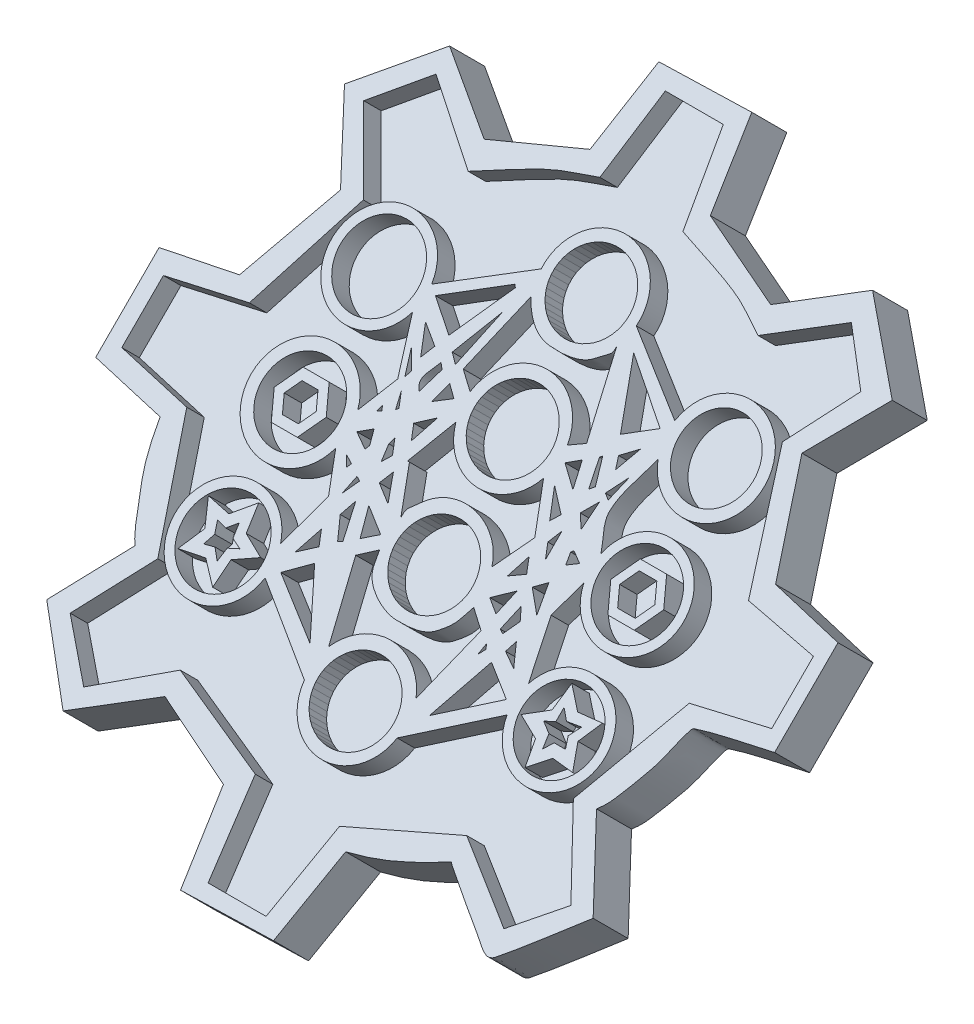
SolidWorks part; units mm, degrees
ref_plane "Front Plane" through (0, 0, 0) normal (0, 0, 1) x (1, 0, 0)
ref_plane "Top Plane" through (0, 0, 0) normal (0, 1, 0) x (1, 0, 0)
ref_plane "Right Plane" through (0, 0, 0) normal (1, 0, 0) x (0, 0, -1)
ref_plane "Plane2" through (0, -6.35, 0) normal (0, 1, 0) x (1, 0, 0)
sketch "Sketch2" plane through (0, -6.35, 0) normal (0, 1, 0) x (1, 0, 0)
  circle A0 centre (0, 0) radius 5.715
  dimension "D1" = 11.43
ref_axis "Axis1" through (-6.2865, 0, 0) along (1, 0, 0)
ref_plane "Plane1" through (0, 0, 0) normal (0, 0.7071, 0.7071) x (1, 0, 0)
sketch "Sketch3" plane through (0, 0, 0) normal (0, 0.7071, 0.7071) x (1, 0, 0)
  line L0 (0, 0) -> (-20.32, 0) construction
  line L1 (-6.2865, 0) -> (6.2865, 0) construction
  line L2 (-20.32, -38.1) -> (-20.32, 38.1) construction
  circle A0 centre (0, 0) radius 19.05
  point P3 (0, 0)
  point P13 (-20.32, 0)
  point P15 (-20.32, 7.62)
  point P16 (-20.32, -7.62)
  point P17 (-20.32, -22.86)
  dimension "D1" = 38.1
  dimension "D4" = 20.32
  dimension "D5" = 76.2
extrude "Boss-Extrude1" add sketch "Sketch3" along normal blind 6.35
extrude "Boss-Extrude2" add sketch "Sketch2" along normal up to surface and the other way blind 3.175 up to face at (0, -13.4704, 13.4704)
sketch "Sketch5" plane through (0, 4.4901, 4.4901) normal (0, 0.7071, 0.7071) x (1, 0, 0)
  line L0 (4.752, 20.3921) -> (4.7809, 21.0328)
  line L1 (4.7809, 21.0328) -> (4.7223, 21.6719)
  line L2 (4.7223, 21.6719) -> (4.5773, 22.2981)
  line L3 (4.5773, 22.2981) -> (4.3485, 22.9001)
  line L4 (4.3485, 22.9001) -> (4.0399, 23.4673)
  line L5 (4.0399, 23.4673) -> (3.6571, 23.9895)
  line L6 (3.6571, 23.9895) -> (3.2069, 24.4575)
  line L7 (3.2069, 24.4575) -> (2.6974, 24.8627)
  line L8 (2.6974, 24.8627) -> (2.1375, 25.1981)
  line L9 (2.1375, 25.1981) -> (1.5374, 25.4576)
  line L10 (1.5374, 25.4576) -> (0.9077, 25.6366)
  line L11 (0.9077, 25.6366) -> (0.2596, 25.732)
  line L12 (0.2596, 25.732) -> (-0.3952, 25.7419)
  line L13 (-0.3952, 25.7419) -> (-1.0451, 25.6662)
  line L14 (-1.0451, 25.6662) -> (-1.6785, 25.5063)
  line L15 (-1.6785, 25.5063) -> (-2.2841, 25.2651)
  line L16 (-2.2841, 25.2651) -> (-2.8511, 24.9468)
  line L17 (-2.8511, 24.9468) -> (-3.3694, 24.5571)
  line L18 (-3.3694, 24.5571) -> (-3.8296, 24.103)
  line L19 (-3.8296, 24.103) -> (-4.2237, 23.5925)
  line L20 (-4.2237, 23.5925) -> (-4.5445, 23.0349)
  line L21 (-4.5445, 23.0349) -> (-4.7864, 22.4399)
  line L22 (-4.7864, 22.4399) -> (-4.945, 21.8184)
  line L23 (-4.945, 21.8184) -> (-5.0175, 21.1812)
  line L24 (-5.0175, 21.1812) -> (-5.0026, 20.5399)
  line L25 (-5.0026, 20.5399) -> (-4.9006, 19.9058)
  line L26 (-4.9006, 19.9058) -> (-4.7133, 19.2903)
  line L27 (-4.7133, 19.2903) -> (-4.444, 18.7044)
  line L28 (-4.444, 18.7044) -> (-4.0976, 18.1585)
  line L29 (-4.0976, 18.1585) -> (-3.6801, 17.6623)
  line L30 (-3.6801, 17.6623) -> (-3.1992, 17.2247)
  line L31 (-3.1992, 17.2247) -> (-2.6633, 16.8536)
  line L32 (-2.6633, 16.8536) -> (-2.082, 16.5554)
  line L33 (-2.082, 16.5554) -> (-1.4657, 16.3357)
  line L34 (-1.4657, 16.3357) -> (-0.8254, 16.1982)
  line L35 (-0.8254, 16.1982) -> (-0.1725, 16.1455)
  line L36 (-0.1725, 16.1455) -> (0.4814, 16.1784)
  line L37 (0.4814, 16.1784) -> (1.1245, 16.2965)
  line L38 (1.1245, 16.2965) -> (1.7453, 16.4975)
  line L39 (1.7453, 16.4975) -> (2.333, 16.7779)
  line L40 (2.333, 16.7779) -> (2.8768, 17.1326)
  line L41 (2.8768, 17.1326) -> (3.3671, 17.5555)
  line L42 (3.3671, 17.5555) -> (3.7953, 18.0389)
  line L43 (3.7953, 18.0389) -> (4.1535, 18.5741)
  line L44 (4.1535, 18.5741) -> (4.4355, 19.1517)
  line L45 (4.4355, 19.1517) -> (4.6362, 19.7613)
  line L46 (4.6362, 19.7613) -> (4.752, 20.3921)
  line L47 (4.7896, 6.4943) -> (4.7689, 7.1365)
  line L48 (4.7689, 7.1365) -> (4.661, 7.7704)
  line L49 (4.661, 7.7704) -> (4.4679, 8.3846)
  line L50 (4.4679, 8.3846) -> (4.1929, 8.9683)
  line L51 (4.1929, 8.9683) -> (3.841, 9.5109)
  line L52 (3.841, 9.5109) -> (3.4185, 10.0029)
  line L53 (3.4185, 10.0029) -> (2.9329, 10.4355)
  line L54 (2.9329, 10.4355) -> (2.3928, 10.8008)
  line L55 (2.3928, 10.8008) -> (1.808, 11.0925)
  line L56 (1.808, 11.0925) -> (1.1888, 11.3053)
  line L57 (1.1888, 11.3053) -> (0.5464, 11.4353)
  line L58 (0.5464, 11.4353) -> (-0.108, 11.4804)
  line L59 (-0.108, 11.4804) -> (-0.7624, 11.4396)
  line L60 (-0.7624, 11.4396) -> (-1.4054, 11.3137)
  line L61 (-1.4054, 11.3137) -> (-2.0254, 11.105)
  line L62 (-2.0254, 11.105) -> (-2.6113, 10.8172)
  line L63 (-2.6113, 10.8172) -> (-3.1527, 10.4553)
  line L64 (-3.1527, 10.4553) -> (-3.6399, 10.026)
  line L65 (-3.6399, 10.026) -> (-4.0643, 9.5368)
  line L66 (-4.0643, 9.5368) -> (-4.4182, 8.9964)
  line L67 (-4.4182, 8.9964) -> (-4.6954, 8.4145)
  line L68 (-4.6954, 8.4145) -> (-4.8909, 7.8016)
  line L69 (-4.8909, 7.8016) -> (-5.0011, 7.1684)
  line L70 (-5.0011, 7.1684) -> (-5.0243, 6.5264)
  line L71 (-5.0243, 6.5264) -> (-4.9598, 5.887)
  line L72 (-4.9598, 5.887) -> (-4.8089, 5.2615)
  line L73 (-4.8089, 5.2615) -> (-4.5744, 4.6612)
  line L74 (-4.5744, 4.6612) -> (-4.2602, 4.0968)
  line L75 (-4.2602, 4.0968) -> (-3.8722, 3.5783)
  line L76 (-3.8722, 3.5783) -> (-3.4171, 3.115)
  line L77 (-3.4171, 3.115) -> (-2.9031, 2.7152)
  line L78 (-2.9031, 2.7152) -> (-2.3394, 2.3859)
  line L79 (-2.3394, 2.3859) -> (-1.7361, 2.1331)
  line L80 (-1.7361, 2.1331) -> (-1.1038, 1.9613)
  line L81 (-1.1038, 1.9613) -> (-0.454, 1.8736)
  line L82 (-0.454, 1.8736) -> (0.2019, 1.8714)
  line L83 (0.2019, 1.8714) -> (0.8521, 1.9549)
  line L84 (0.8521, 1.9549) -> (1.4849, 2.1226)
  line L85 (1.4849, 2.1226) -> (2.0892, 2.3714)
  line L86 (2.0892, 2.3714) -> (2.6541, 2.697)
  line L87 (2.6541, 2.697) -> (3.1696, 3.0935)
  line L88 (3.1696, 3.0935) -> (3.6264, 3.5538)
  line L89 (3.6264, 3.5538) -> (4.0164, 4.0698)
  line L90 (4.0164, 4.0698) -> (4.3327, 4.6321)
  line L91 (4.3327, 4.6321) -> (4.5696, 5.2309)
  line L92 (4.5696, 5.2309) -> (4.7228, 5.8553)
  line L93 (4.7228, 5.8553) -> (4.7896, 6.4943)
  line L94 (4.7659, -7.8572) -> (4.7628, -7.2151)
  line L95 (4.7628, -7.2151) -> (4.6722, -6.5789)
  line L96 (4.6722, -6.5789) -> (4.4959, -5.96)
  line L97 (4.4959, -5.96) -> (4.237, -5.3693)
  line L98 (4.237, -5.3693) -> (3.9001, -4.8176)
  line L99 (3.9001, -4.8176) -> (3.4912, -4.3145)
  line L100 (3.4912, -4.3145) -> (3.0176, -3.8691)
  line L101 (3.0176, -3.8691) -> (2.4878, -3.4894)
  line L102 (2.4878, -3.4894) -> (1.9112, -3.182)
  line L103 (1.9112, -3.182) -> (1.2981, -2.9525)
  line L104 (1.2981, -2.9525) -> (0.6595, -2.805)
  line L105 (0.6595, -2.805) -> (0.0068, -2.7421)
  line L106 (0.0068, -2.7421) -> (-0.6485, -2.7649)
  line L107 (-0.6485, -2.7649) -> (-1.2946, -2.8731)
  line L108 (-1.2946, -2.8731) -> (-1.92, -3.0647)
  line L109 (-1.92, -3.0647) -> (-2.5135, -3.3362)
  line L110 (-2.5135, -3.3362) -> (-3.0645, -3.6829)
  line L111 (-3.0645, -3.6829) -> (-3.5632, -4.0985)
  line L112 (-3.5632, -4.0985) -> (-4.0007, -4.5756)
  line L113 (-4.0007, -4.5756) -> (-4.3692, -5.1058)
  line L114 (-4.3692, -5.1058) -> (-4.6622, -5.6795)
  line L115 (-4.6622, -5.6795) -> (-4.8743, -6.2866)
  line L116 (-4.8743, -6.2866) -> (-5.0018, -6.9161)
  line L117 (-5.0018, -6.9161) -> (-5.0424, -7.5568)
  line L118 (-5.0424, -7.5568) -> (-4.9954, -8.1974)
  line L119 (-4.9954, -8.1974) -> (-4.8617, -8.8264)
  line L120 (-4.8617, -8.8264) -> (-4.6436, -9.4325)
  line L121 (-4.6436, -9.4325) -> (-4.345, -10.005)
  line L122 (-4.345, -10.005) -> (-3.9713, -10.5336)
  line L123 (-3.9713, -10.5336) -> (-3.5291, -11.0088)
  line L124 (-3.5291, -11.0088) -> (-3.0263, -11.4223)
  line L125 (-3.0263, -11.4223) -> (-2.4718, -11.7667)
  line L126 (-2.4718, -11.7667) -> (-1.8757, -12.0357)
  line L127 (-1.8757, -12.0357) -> (-1.2484, -12.2246)
  line L128 (-1.2484, -12.2246) -> (-0.6013, -12.3301)
  line L129 (-0.6013, -12.3301) -> (0.0542, -12.3501)
  line L130 (0.0542, -12.3501) -> (0.7063, -12.2845)
  line L131 (0.7063, -12.2845) -> (1.3435, -12.1343)
  line L132 (1.3435, -12.1343) -> (1.9543, -11.9022)
  line L133 (1.9543, -11.9022) -> (2.5278, -11.5924)
  line L134 (2.5278, -11.5924) -> (3.0539, -11.2104)
  line L135 (3.0539, -11.2104) -> (3.523, -10.763)
  line L136 (3.523, -10.763) -> (3.9269, -10.2583)
  line L137 (3.9269, -10.2583) -> (4.2584, -9.7051)
  line L138 (4.2584, -9.7051) -> (4.5115, -9.1134)
  line L139 (4.5115, -9.1134) -> (4.6817, -8.4937)
  line L140 (4.6817, -8.4937) -> (4.7659, -7.8572)
  line L141 (4.6885, -22.7943) -> (4.7728, -22.1691)
  line L142 (4.7728, -22.1691) -> (4.7731, -21.5377)
  line L143 (4.7731, -21.5377) -> (4.6896, -20.9111)
  line L144 (4.6896, -20.9111) -> (4.5237, -20.3)
  line L145 (4.5237, -20.3) -> (4.2781, -19.7148)
  line L146 (4.2781, -19.7148) -> (3.9571, -19.1654)
  line L147 (3.9571, -19.1654) -> (3.5662, -18.6615)
  line L148 (3.5662, -18.6615) -> (3.1121, -18.2114)
  line L149 (3.1121, -18.2114) -> (2.6025, -17.823)
  line L150 (2.6025, -17.823) -> (2.0462, -17.503)
  line L151 (2.0462, -17.503) -> (1.4526, -17.2566)
  line L152 (1.4526, -17.2566) -> (0.832, -17.0883)
  line L153 (0.832, -17.0883) -> (0.195, -17.0008)
  line L154 (0.195, -17.0008) -> (-0.4477, -16.9957)
  line L155 (-0.4477, -16.9957) -> (-1.0848, -17.0731)
  line L156 (-1.0848, -17.0731) -> (-1.7056, -17.2315)
  line L157 (-1.7056, -17.2315) -> (-2.2995, -17.4684)
  line L158 (-2.2995, -17.4684) -> (-2.8562, -17.7796)
  line L159 (-2.8562, -17.7796) -> (-3.3663, -18.1599)
  line L160 (-3.3663, -18.1599) -> (-3.8209, -18.6027)
  line L161 (-3.8209, -18.6027) -> (-4.2124, -19.1005)
  line L162 (-4.2124, -19.1005) -> (-4.5341, -19.6447)
  line L163 (-4.5341, -19.6447) -> (-4.7803, -20.226)
  line L164 (-4.7803, -20.226) -> (-4.947, -20.8345)
  line L165 (-4.947, -20.8345) -> (-5.0313, -21.4598)
  line L166 (-5.0313, -21.4598) -> (-5.0316, -22.0911)
  line L167 (-5.0316, -22.0911) -> (-4.9481, -22.7177)
  line L168 (-4.9481, -22.7177) -> (-4.7822, -23.3289)
  line L169 (-4.7822, -23.3289) -> (-4.5366, -23.9141)
  line L170 (-4.5366, -23.9141) -> (-4.2156, -24.4634)
  line L171 (-4.2156, -24.4634) -> (-3.8247, -24.9674)
  line L172 (-3.8247, -24.9674) -> (-3.3706, -25.4174)
  line L173 (-3.3706, -25.4174) -> (-2.861, -25.8058)
  line L174 (-2.861, -25.8058) -> (-2.3047, -26.1259)
  line L175 (-2.3047, -26.1259) -> (-1.7111, -26.3722)
  line L176 (-1.7111, -26.3722) -> (-1.0905, -26.5406)
  line L177 (-1.0905, -26.5406) -> (-0.4535, -26.628)
  line L178 (-0.4535, -26.628) -> (0.1892, -26.6331)
  line L179 (0.1892, -26.6331) -> (0.8263, -26.5558)
  line L180 (0.8263, -26.5558) -> (1.4471, -26.3973)
  line L181 (1.4471, -26.3973) -> (2.041, -26.1605)
  line L182 (2.041, -26.1605) -> (2.5977, -25.8492)
  line L183 (2.5977, -25.8492) -> (3.1077, -25.4689)
  line L184 (3.1077, -25.4689) -> (3.5624, -25.0261)
  line L185 (3.5624, -25.0261) -> (3.9539, -24.5284)
  line L186 (3.9539, -24.5284) -> (4.2756, -23.9842)
  line L187 (4.2756, -23.9842) -> (4.5218, -23.4028)
  line L188 (4.5218, -23.4028) -> (4.6885, -22.7943)
  line L189 (24.8479, -12.3431) -> (21.8328, -12.5941)
  line L190 (20.2723, -12.8442) -> (20.2723, -14.3477)
  line L191 (20.2723, -14.3477) -> (19.0724, -14.8441)
  line L192 (19.0724, -14.8441) -> (20.2723, -15.5945)
  line L193 (20.2723, -15.5945) -> (20.5213, -17.0883)
  line L194 (20.5213, -17.0883) -> (21.2872, -16.0803)
  line L195 (21.2872, -16.0803) -> (22.7399, -16.0803)
  line L196 (22.7399, -16.0803) -> (22.2468, -14.8881)
  line L197 (22.2468, -14.8881) -> (23.0549, -13.596)
  line L198 (23.0549, -13.596) -> (21.2872, -13.8378)
  line L199 (21.2872, -13.8378) -> (20.2723, -12.8442)
  line L200 (23.4909, -14.8881) -> (24.8479, -12.3431)
  line L201 (24.7185, -17.5812) -> (23.4909, -14.8881)
  line L202 (22.0136, -17.3571) -> (24.7185, -17.5812)
  line L203 (19.851, -19.3442) -> (22.0136, -17.3571)
  line L204 (19.2587, -16.5944) -> (19.851, -19.3442)
  line L205 (16.5326, -15.3548) -> (19.2587, -16.5944)
  line L206 (19.2587, -13.596) -> (16.5326, -15.3548)
  line L207 (19.6724, -10.5942) -> (19.2587, -13.596)
  line L208 (21.8328, -12.5941) -> (19.6724, -10.5942)
  line L209 (17.6546, -0.6678) -> (19.3497, -3.6038)
  line L210 (23.3049, -0.6678) -> (22.1748, 1.2895)
  line L211 (22.1748, 1.2895) -> (19.9148, 1.2895)
  line L212 (19.9148, 1.2895) -> (18.7848, -0.6678)
  line L213 (18.7848, -0.6678) -> (19.9148, -2.625)
  line L214 (19.9148, -2.625) -> (22.1748, -2.625)
  line L215 (22.1748, -2.625) -> (23.3049, -0.6678)
  line L216 (19.3497, 2.2683) -> (17.6546, -0.6678)
  line L217 (22.7399, 2.2683) -> (19.3497, 2.2683)
  line L218 (24.4351, -0.6678) -> (22.7399, 2.2683)
  line L219 (22.7399, -3.6038) -> (24.4351, -0.6678)
  line L220 (19.3497, -3.6038) -> (22.7399, -3.6038)
  line L221 (-25.3936, -0.8442) -> (-23.7252, -3.7338)
  line L222 (-20.0031, -0.8442) -> (-21.03, 0.9345)
  line L223 (-21.03, 0.9345) -> (-23.0838, 0.9345)
  line L224 (-23.0838, 0.9345) -> (-24.1107, -0.8442)
  line L225 (-24.1107, -0.8442) -> (-23.0838, -2.6229)
  line L226 (-23.0838, -2.6229) -> (-21.03, -2.6229)
  line L227 (-21.03, -2.6229) -> (-20.0031, -0.8442)
  line L228 (-23.7252, 2.0454) -> (-25.3936, -0.8442)
  line L229 (-20.3886, 2.0454) -> (-23.7252, 2.0454)
  line L230 (-18.7203, -0.8442) -> (-20.3886, 2.0454)
  line L231 (-20.3886, -3.7338) -> (-18.7203, -0.8442)
  line L232 (-23.7252, -3.7338) -> (-20.3886, -3.7338)
  line L233 (-22.2094, -16.0803) -> (-23.47, -16.3518)
  line L234 (-25.7003, -12.3431) -> (-22.7183, -12.8442)
  line L235 (-22.7183, -12.8442) -> (-20.4566, -10.6217)
  line L236 (-20.4566, -10.6217) -> (-19.9608, -13.5962)
  line L237 (-19.9608, -13.5962) -> (-17.2315, -14.8373)
  line L238 (-17.2315, -14.8373) -> (-19.9608, -16.3518)
  line L239 (-19.9608, -16.3518) -> (-20.2087, -19.3442)
  line L240 (-20.2087, -19.3442) -> (-22.5006, -17.3571)
  line L241 (-22.5006, -17.3571) -> (-25.7003, -17.8904)
  line L242 (-25.7003, -17.8904) -> (-24.2093, -15.0942)
  line L243 (-24.2093, -15.0942) -> (-25.7003, -12.3431)
  line L244 (-21.2188, -17.0883) -> (-22.2094, -16.0803)
  line L245 (-20.9713, -15.6153) -> (-21.2188, -17.0883)
  line L246 (-19.722, -15.0942) -> (-20.9713, -15.6153)
  line L247 (-20.9713, -14.5803) -> (-19.722, -15.0942)
  line L248 (-21.2188, -13.0953) -> (-20.9713, -14.5803)
  line L249 (-22.2383, -14.0971) -> (-21.2188, -13.0953)
  line L250 (-23.47, -13.8437) -> (-22.2383, -14.0971)
  line L251 (-22.9527, -15.0942) -> (-23.47, -13.8437)
  line L252 (-23.47, -16.3518) -> (-22.9527, -15.0942)
  line L253 (5.5702, 4.2261) -> (8.0297, -0.8442)
  line L254 (8.0297, -10.5942) -> (5.5297, -18.8442)
  line L255 (-8.2203, 9.1558) -> (-6.3032, 7.6899)
  line L256 (13.7797, 8.1558) -> (12.3445, 5.8534)
  line L257 (-14.4703, 8.6558) -> (-13.4067, 5.9058)
  line L258 (12.2797, 4.9058) -> (11.0297, 3.1558)
  line L259 (-7.6085, 15.39) -> (-10.2203, 9.9844)
  line L260 (-7.7203, 17.9058) -> (-11.4703, 11.1558)
  line L261 (7.2797, 18.1558) -> (14.0297, 13.4058)
  line L262 (-14.4703, 11.1558) -> (-12.2203, 9.6558)
  line L263 (11.0297, 5.9058) -> (10.5297, 5.4058)
  line L264 (-8.7203, 7.4058) -> (-7.4703, 6.4058)
  line L265 (8.2797, 7.4058) -> (9.0297, 4.6558)
  line L266 (-12.9703, 4.6558) -> (-12.2203, 3.1558)
  line L267 (-7.9703, 4.1558) -> (-9.2203, 1.1558)
  line L268 (7.0297, 4.1558) -> (9.2797, 2.1558)
  line L269 (-13.9703, 2.6558) -> (-13.7203, 2.1558)
  line L270 (10.2797, 0.9058) -> (10.2797, -2.0942)
  line L271 (-10.2203, -0.8442) -> (-10.9703, -1.8442)
  line L272 (-12.9703, -1.0942) -> (-13.2203, -1.5942)
  line L273 (13.7797, -0.8442) -> (12.5297, -1.5942)
  line L274 (-9.2203, -2.0942) -> (-7.9703, -4.8442)
  line L275 (8.5297, -2.5942) -> (9.2797, -4.0942)
  line L276 (-14.7203, -2.8442) -> (-13.7203, -3.3442)
  line L277 (-12.4703, -4.0942) -> (-11.9703, -4.3442)
  line L278 (-9.7203, -5.8442) -> (-6.9703, -7.5942)
  line L279 (9.2797, -5.8442) -> (8.5297, -8.5942)
  line L280 (-10.2203, -9.8442) -> (-10.7203, -10.0942)
  line L281 (11.2797, -8.0942) -> (10.2797, -9.8442)
  line L282 (-12.9703, -9.8442) -> (-12.2203, -11.3442)
  line L283 (12.0297, -9.8442) -> (13.2797, -12.0942)
  line L284 (10.7797, -12.5942) -> (14.2797, -14.8442)
  line L285 (-11.7203, -12.8442) -> (-7.7203, -19.3442)
  line L286 (10.5297, -4.8442) -> (11.8822, -3.7384)
  line L287 (-10.7203, 8.6558) -> (-10.2203, 8.1558)
  line L288 (6.0297, -9.0942) -> (8.0297, -10.5942)
  line L289 (-8.2203, -10.3442) -> (-6.2203, -8.8442)
  line L290 (-5.7444, -18.7621) -> (-8.2203, -10.3442)
  line L291 (7.7797, 8.9058) -> (6.0297, 7.9058)
  line L292 (5.2797, 17.9058) -> (7.7797, 8.9058)
  line L293 (-8.2203, 9.1558) -> (-5.7203, 17.9058)
  line L294 (12.3445, 5.8534) -> (13.0013, 5.444)
  line L295 (13.0013, 5.444) -> (13.7797, 8.1558)
  line L296 (-13.0788, 6.6711) -> (-14.4703, 8.6558)
  line L297 (11.0297, 3.1558) -> (12.0297, 1.9058)
  line L298 (12.0297, 1.9058) -> (12.2797, 4.9058)
  line L299 (-10.2203, 9.9844) -> (-9.2203, 9.1558)
  line L300 (-9.2203, 9.1558) -> (-7.6085, 15.39)
  line L301 (-7.9703, 18.1558) -> (-7.7203, 17.9058)
  line L302 (-14.9703, 13.6558) -> (-7.9703, 18.1558)
  line L303 (-11.4703, 11.1558) -> (-14.9703, 13.6558)
  line L304 (10.5297, 11.1558) -> (7.2797, 18.1558)
  line L305 (14.0297, 13.4058) -> (10.5297, 11.1558)
  line L306 (-12.9703, 8.1558) -> (-14.4703, 11.1558)
  line L307 (-12.2203, 9.6558) -> (-12.9703, 8.1558)
  line L308 (11.5297, 9.4058) -> (13.2797, 10.9058)
  line L309 (12.0297, 8.1558) -> (11.5297, 9.4058)
  line L310 (10.0297, 8.6558) -> (11.0297, 5.9058)
  line L311 (9.7797, 8.4058) -> (10.0297, 8.6558)
  line L312 (10.5297, 5.4058) -> (9.7797, 8.4058)
  line L313 (-9.4703, 5.1558) -> (-8.7203, 7.4058)
  line L314 (-7.4703, 6.4058) -> (-9.4703, 5.1558)
  line L315 (6.7797, 6.4058) -> (8.2797, 7.4058)
  line L316 (9.0297, 4.6558) -> (6.7797, 6.4058)
  line L317 (-12.4703, 2.9058) -> (-12.9703, 4.6558)
  line L318 (-12.2203, 3.1558) -> (-12.4703, 2.9058)
  line L319 (-9.9703, 2.6558) -> (-7.9703, 4.1558)
  line L320 (-9.2203, 1.1558) -> (-9.9703, 2.6558)
  line L321 (8.5297, 1.1558) -> (7.0297, 4.1558)
  line L322 (9.2797, 2.1558) -> (8.5297, 1.1558)
  line L323 (-14.2203, 1.9058) -> (-13.9703, 2.6558)
  line L324 (-13.7203, 2.1558) -> (-14.2203, 1.9058)
  line L325 (9.5297, -0.5942) -> (10.2797, 0.9058)
  line L326 (10.2797, -2.0942) -> (9.5297, -0.5942)
  line L327 (-10.9703, 0.6558) -> (-10.2203, -0.8442)
  line L328 (-11.2203, -0.0942) -> (-10.9703, 0.6558)
  line L329 (-10.9703, -1.8442) -> (-11.2203, -0.0942)
  line L330 (-13.4703, 0.4058) -> (-12.9703, -1.0942)
  line L331 (-14.9703, -0.5942) -> (-13.4703, 0.4058)
  line L332 (-13.2203, -1.5942) -> (-14.9703, -0.5942)
  line L333 (12.5297, -0.0942) -> (13.7797, -0.8442)
  line L334 (12.2797, -0.3442) -> (12.5297, -0.0942)
  line L335 (12.5297, -1.5942) -> (12.2797, -0.3442)
  line L336 (-9.9703, -3.5942) -> (-9.2203, -2.0942)
  line L337 (-7.9703, -4.8442) -> (-9.9703, -3.5942)
  line L338 (7.5297, -5.0942) -> (8.5297, -2.5942)
  line L339 (9.2797, -4.0942) -> (7.5297, -5.0942)
  line L340 (-13.9703, -3.8442) -> (-14.7203, -2.8442)
  line L341 (-13.7203, -3.3442) -> (-13.9703, -3.8442)
  line L342 (-12.9703, -6.0942) -> (-12.4703, -4.0942)
  line L343 (-11.9703, -4.3442) -> (-12.9703, -6.0942)
  line L344 (-8.7203, -8.8442) -> (-9.7203, -5.8442)
  line L345 (-6.9703, -7.5942) -> (-8.7203, -8.8442)
  line L346 (7.0297, -7.5942) -> (9.2797, -5.8442)
  line L347 (8.5297, -8.5942) -> (7.0297, -7.5942)
  line L348 (-11.2203, -6.0942) -> (-10.2203, -9.8442)
  line L349 (-11.9703, -7.8442) -> (-11.2203, -6.0942)
  line L350 (-10.7203, -10.0942) -> (-11.9703, -7.8442)
  line L351 (10.5297, -6.8442) -> (11.2797, -8.0942)
  line L352 (9.7797, -9.5942) -> (10.5297, -6.8442)
  line L353 (10.2797, -9.8442) -> (9.7797, -9.5942)
  line L354 (-14.2203, -12.8442) -> (-12.9703, -9.8442)
  line L355 (-12.2203, -11.3442) -> (-14.2203, -12.8442)
  line L356 (11.5297, -11.0942) -> (12.0297, -9.8442)
  line L357 (13.2797, -12.0942) -> (11.5297, -11.0942)
  line L358 (9.0297, -12.5942) -> (9.2797, -11.3442)
  line L359 (9.5297, -11.8442) -> (9.0297, -12.5942)
  line L360 (7.7797, -19.5942) -> (10.7797, -12.5942)
  line L361 (14.2797, -14.8442) -> (7.7797, -19.5942)
  line L362 (-14.4703, -15.0942) -> (-11.7203, -12.8442)
  line L363 (-7.7203, -19.3442) -> (-14.4703, -15.0942)
  line L364 (12.5297, -6.8442) -> (10.5297, -4.8442)
  line L365 (11.8822, -3.7384) -> (12.5297, -6.8442)
  line L366 (15.5297, -12.5941) -> (13.9053, -6.1927)
  line L367 (15.2067, -16.0254) -> (5.9154, -22.8161)
  line L368 (-6.2203, -22.4786) -> (-15.6775, -16.2353)
  line L369 (-16.0891, -12.8442) -> (-14.102, -6.9611)
  line L370 (-14.102, -6.9611) -> (-16.0891, -2.8442)
  line L371 (-16.0891, 1.1558) -> (-13.9703, 5.4059)
  line L372 (-16.2575, 11.3199) -> (-13.9703, 5.4059)
  line L373 (-15.9703, 14.3885) -> (-6.2823, 20.5535)
  line L374 (6.0297, 20.3921) -> (15.0022, 14.687)
  line L375 (-10.2203, 8.1558) -> (-11.2203, 5.4058)
  line L376 (-8.4703, -0.5942) -> (-5.9703, 4.6558)
  line L377 (-8.2203, -0.5942) -> (-8.4703, -0.5942)
  line L378 (-5.9703, -5.3442) -> (-8.2203, -0.5942)
  line L379 (8.0297, -0.8442) -> (5.5297, -5.0942)
  line L380 (13.2797, 10.9058) -> (12.0297, 8.1558)
  line L381 (9.2797, -11.3442) -> (9.5297, -11.8442)
  line L382 (13.9053, -6.1927) -> (15.2622, -2.1756)
  line L383 (-13.4067, 5.9058) -> (-13.0788, 6.6711)
  line L384 (-27.2203, 17.9058) -> (-32.4703, 4.6558)
  line L385 (-42.2534, 2.9058) -> (-32.4703, 4.6558)
  line L386 (-27.0649, -19.5942) -> (-32.6919, -6.3806)
  line L387 (-27.0649, -33.0252) -> (-32.4703, -27.8442)
  line L388 (-32.6919, 25.7161) -> (-27.2203, 17.9058)
  line L389 (-18.7203, -27.3248) -> (-5.7203, -32.0942)
  line L390 (-4.2203, -42.7729) -> (-5.7203, -32.0942)
  line L391 (-4.2203, -42.7729) -> (3.2109, -42.7729)
  line L392 (3.2109, -42.7729) -> (5.2797, -32.3652)
  line L393 (-42.2534, -4.6424) -> (-32.6919, -6.3806)
  line L394 (18.0297, -27.3248) -> (26.7797, -32.9582)
  line L395 (31.9281, -28.0942) -> (26.7797, -32.9582)
  line L396 (26.231, -19.5942) -> (31.9281, -28.0942)
  line L397 (-27.0649, -33.0252) -> (-18.7203, -27.3248)
  line L398 (41.4226, -5.0942) -> (32.0819, -6.8442)
  line L399 (41.4226, 2.4688) -> (41.4226, -5.0942)
  line L400 (32.0819, 3.9058) -> (41.4226, 2.4688)
  line L401 (-42.2534, -4.6424) -> (-42.2534, 2.9058)
  line L402 (31.2797, 25.4058) -> (26.5297, 17.9058)
  line L403 (26.5297, 30.4058) -> (31.2797, 25.4058)
  line L404 (-32.4703, -27.8442) -> (-27.0649, -19.5942)
  line L405 (3.2109, 40.1558) -> (5.2797, 29.9058)
  line L406 (-4.2203, 40.1558) -> (3.2109, 40.1558)
  line L407 (-5.7203, 30.4058) -> (-4.2203, 40.1558)
  line L408 (-27.2203, 31.0785) -> (-18.7203, 24.9058)
  line L409 (5.2797, -44.3442) -> (7.2797, -34.0942)
  line L410 (5.2797, -44.3442) -> (-6.4703, -44.5942)
  line L411 (-8.2203, -34.3442) -> (-6.4703, -44.5942)
  line L412 (32.0819, -6.8442) -> (26.231, -19.5942)
  line L413 (-27.7203, -35.8442) -> (-18.7203, -30.0942)
  line L414 (-35.4703, -27.8442) -> (-27.7203, -35.8442)
  line L415 (-29.9703, -19.5942) -> (-35.4703, -27.8442)
  line L416 (-44.2203, -6.5942) -> (-34.7203, -8.3442)
  line L417 (-44.2203, -6.5942) -> (-44.2203, 4.9058)
  line L418 (-34.9703, 6.4058) -> (-44.2203, 4.9058)
  line L419 (-29.9703, 17.6558) -> (-34.9703, 6.4058)
  line L420 (-35.4703, 26.1558) -> (-29.9703, 17.6558)
  line L421 (-27.4703, 33.9058) -> (-35.4703, 26.1558)
  line L422 (-18.9703, 28.1558) -> (-27.4703, 33.9058)
  line L423 (-8.2203, 32.1558) -> (-18.9703, 28.1558)
  line L424 (-6.4703, 42.1558) -> (-8.2203, 32.1558)
  line L425 (5.2797, -32.3652) -> (18.0297, -27.3248)
  line L426 (7.0297, 32.4058) -> (5.2797, 42.4058)
  line L427 (17.7797, 28.1558) -> (7.0297, 32.4058)
  line L428 (26.7797, 33.9058) -> (17.7797, 28.1558)
  line L429 (34.7797, 26.1558) -> (26.7797, 33.9058)
  line L430 (29.0297, 17.9058) -> (34.7797, 26.1558)
  line L431 (33.7797, 6.4058) -> (29.0297, 17.9058)
  line L432 (43.0297, 4.6558) -> (33.7797, 6.4058)
  line L433 (43.0297, 4.6558) -> (43.0297, -6.8442)
  line L434 (34.7797, -28.0942) -> (29.0297, -19.3442)
  line L435 (18.2797, 25.1558) -> (26.5297, 30.4058)
  line L436 (-32.6919, 25.7161) -> (-27.2203, 31.0785)
  line L437 (26.5297, 17.9058) -> (32.0819, 3.9058)
  line L438 (-18.7203, -30.0942) -> (-8.2203, -34.3442)
  line L439 (-6.4703, 42.1558) -> (5.2797, 42.4058)
  circle A0 centre (21.091, 13.6092) radius 4.8057
  circle A1 centre (-22.0569, -0.8442) radius 4.871
  circle A2 centre (21.0448, -0.6678) radius 4.8556
  circle A3 centre (-21.7684, -15.254) radius 5.0383
  circle A4 centre (-22.0086, 13.4059) radius 4.9706
  circle A5 centre (21.0448, -14.8441) radius 4.8094
  arc A6 (5.5297, -18.8442) -> (-5.7444, -18.7621) centre (-0.1293, -21.8144) ccw
  arc A7 (6.0297, 7.9058) -> (-6.3032, 7.6899) centre (-0.117, 6.6711) ccw
  arc A8 (15.2067, -16.0254) -> (15.5297, -12.5941) centre (21.0448, -14.8441) ccw
  arc A9 (-6.2203, -22.4786) -> (5.9154, -22.8161) centre (-0.1293, -21.8144) ccw
  arc A10 (-16.0891, -12.8442) -> (-15.6775, -16.2353) centre (-21.7684, -15.254) ccw
  arc A11 (-16.0891, 1.1558) -> (-16.0891, -2.8442) centre (-22.0569, -0.8442) ccw
  arc A12 (-15.9703, 14.3885) -> (-16.2575, 11.3199) centre (-22.0086, 13.4059) ccw
  arc A13 (6.0297, 20.3921) -> (-6.2823, 20.5535) centre (-0.1201, 20.9466) ccw
  arc A14 (15.5297, 10.9059) -> (15.0022, 14.687) centre (21.091, 13.6092) ccw
  arc A15 (15.2622, -2.1756) -> (15.2797, 0.9059) centre (21.0448, -0.6678) ccw
  arc A16 (-5.9703, 4.6558) -> (5.5702, 4.2261) centre (-0.117, 6.6711) ccw
  spline S0 degree 3 poles (-6.2203, -8.8442) (-6.0536, -9.5109) (-6.0046, -10.2186) (-5.7203, -10.8442) (-4.9883, -12.4544) (-2.3331, -13.5942) (-0.7203, -13.5942) (0.6249, -13.5942) (2.6103, -13.6467) (3.7797, -12.5942) (5.3369, -11.1928) (5.2711, -10.8644) (6.0297, -9.0942) knots 0 0 0 0 1 1 1 2 2 2 3 3 3 4 4 4 4
  spline S1 degree 3 poles (-5.7203, 17.9058) (-4.6768, 16.3406) (-3.272, 15.0768) (-1.2203, 14.9058) (0.0803, 14.7974) (2.5327, 14.7835) (3.7797, 15.9058) (5.334, 17.3046) (5.2797, 16.9325) (5.2797, 17.9058) knots 0 0 0 0 1 1 1 2 2 2 3 3 3 3
  spline S2 degree 3 poles (15.2797, 0.9059) (14.7703, 2.1627) (13.7175, 3.3205) (13.7513, 4.6762) (13.8053, 6.835) (14.9369, 8.8293) (15.5297, 10.9059) knots 0 0 0 0 1 1 1 2 2 2 2
  spline S3 degree 3 poles (-11.2203, 5.4058) (-12.298, 6.4835) (-11.2995, 7.3524) (-10.7203, 8.6558) knots 0 0 0 0 1 1 1 1
  spline S4 degree 3 poles (5.5297, -5.0942) (3.9995, -1.2686) (-1.7784, 0.1151) (-4.7203, -3.0942) (-6.0144, -4.506) (-5.9703, -4.3779) (-5.9703, -5.3442) knots 0 0 0 0 1 1 1 2 2 2 2
  spline S5 degree 3 poles (18.0297, -30.0942) (18.1131, -30.1775) (18.1828, -30.2771) (18.2797, -30.3442) (20.2355, -31.6982) (22.5353, -33.2978) (24.5297, -34.5942) (25.1889, -35.0226) (25.7839, -35.5956) (26.5297, -35.8442) (26.8557, -35.9529) (27.2793, -35.8294) (27.5297, -35.5942) (30.064, -33.2135) (32.3631, -30.5942) (34.7797, -28.0942) knots 0 0 0 0 1 1 1 2 2 2 3 3 3 4 4 4 5 5 5 5
  spline S6 degree 3 poles (5.2797, 29.9058) (8.1131, 29.0725) (11.0058, 28.4194) (13.7797, 27.4058) (15.3549, 26.8303) (16.7797, 25.9058) (18.2797, 25.1558) knots 0 0 0 0 1 1 1 2 2 2 2
  spline S7 degree 3 poles (-18.7203, 24.9058) (-16.2203, 26.1558) (-13.7944, 27.5667) (-11.2203, 28.6558) (-9.4484, 29.4054) (-7.5536, 29.8225) (-5.7203, 30.4058) knots 0 0 0 0 1 1 1 2 2 2 2
  spline S8 degree 3 poles (7.2797, -34.0942) (11.5848, -33.2332) (14.1447, -32.0367) (18.0297, -30.0942) knots 0 0 0 0 1 1 1 1
  spline S9 degree 3 poles (-34.7203, -8.3442) (-34.2934, -10.4787) (-33.7313, -12.6984) (-32.7203, -14.5942) (-32.4552, -15.0911) (-30.9409, -18.6235) (-29.9703, -19.5942) knots 0 0 0 0 1 1 1 2 2 2 2
  spline S10 degree 3 poles (29.0297, -19.3442) (29.5356, -18.8383) (29.9704, -18.2129) (30.2797, -17.5942) (30.9799, -16.1938) (31.7059, -14.8009) (32.2797, -13.3442) (32.7917, -12.0445) (33.0468, -10.655) (33.5297, -9.3442) (33.6336, -9.0623) (33.7392, -8.6707) (34.0297, -8.5942) (36.9853, -7.8164) (40.0297, -7.4275) (43.0297, -6.8442) knots 0 0 0 0 1 1 1 2 2 2 3 3 3 4 4 4 5 5 5 5
  circle M1 centre (0, 0) radius 19.05
extrude "Boss-Extrude3" add sketch "Sketch5" along normal blind 3.175 contours L422 L421 L420 L419 L418 L417 L416 S9 L415 L414 L413 L438 L411 L410 L409 S8 S5 L434 S10 L433 L432 L431 L430 L429 L428 L427 L426 L439 L424 L423
extrude "Boss-Extrude4" add sketch "Sketch5<3>" along normal blind 6.35 contours L434 S10 L433 L432 L431 L430 L429 L428 L427 L426 L439 L424 L423 L422 L421 L420 L419 L418 L417 L416 S9 L415 L414 L413 L438 L411 L410 L409 S8 S5 L408 S7 L407 L406 L405 S6 L435 L403 L402 L437 L400 L399 L398 L412 L396 L395 L394 L425 L392 L391 | A14 L374 A13 L373 A12 L372 L303 L302 L301 L260 L28 L27 L26 L25 L24 L23 L22 L21 L20 L19 L18 L17 L16 L15 L14 L13 L12 L11 L10 L9 L8 L7 L6 L5 L4 L3 L2 L1 L0 L46 L45 L44 L304 L261 L305 M1 | L221 L232 L231 L230 L229 L228 L227 L226 L225 L224 L223 L222 M1 | L243 L242 L241 L240 L239 L238 L237 L236 L235 L234 L233 L252 L251 L250 L249 L248 L247 L246 L245 L244 | L209 L220 L219 L218 L217 L216 L212 L211 L210 L215 L214 L213 M1 | L189 L208 L207 L206 L205 L204 L203 L202 L201 L200 L199 L198 L197 L196 L195 L194 L193 L192 L191 L190 | A15 S2 A14 L305 L304 L44 L43 L42 L41 L40 L39 L38 L37 L36 L35 L34 L33 L32 L31 L30 L29 L28 L260 L303 L372 L371 A11 A1 L370 L369 L354 L282 L355 L362 L285 L290 L289 S0 L288 L254 M1 | L369 A10 L368 A9 L367 A8 L366 L284 L361 L360 L254 A6 L147 L146 L145 L144 L143 L142 L141 L188 L187 L186 L185 L184 L183 L182 L181 L180 L179 L178 L177 L176 L175 L174 L173 L172 L171 L170 L169 L168 L167 L166 L165 L164 L163 L162 L161 M1 | A6 L161 L160 L159 L158 L157 L156 L155 L154 L153 L152 L151 L150 L149 L148 L147 M1 | A11 A1 M1 | A15 A2 M1 | L216 L209 L213 L212 M1 | L231 L230 M1 region at (5.3543, 19.1173, -10.137) region at (5.7437, 16.9434, -7.9632) region at (26.8689, 3.8873, 5.093) region at (-18.8662, 7.0561, 1.9241) region at (15.9464, -3.9045, 12.8848) region at (18.5362, 4.075, 4.9053) region at (19.2352, 5.8391, 3.1411) region at (-19.119, 3.9178, 5.0624) region at (-18.9271, 3.9118, 5.0685) region at (-0.0853, -7.4932, 16.4735) region at (24.0629, -5.0974, 14.0776) region at (-24.2294, -4.4997, 13.48) region at (-0.6215, -26.0833, 35.0635)
sketch "Sketch5<3>" plane through (0, 4.4901, 4.4901) normal (0, 0.7071, 0.7071) x (1, 0, 0) same geometry as "Sketch5"
